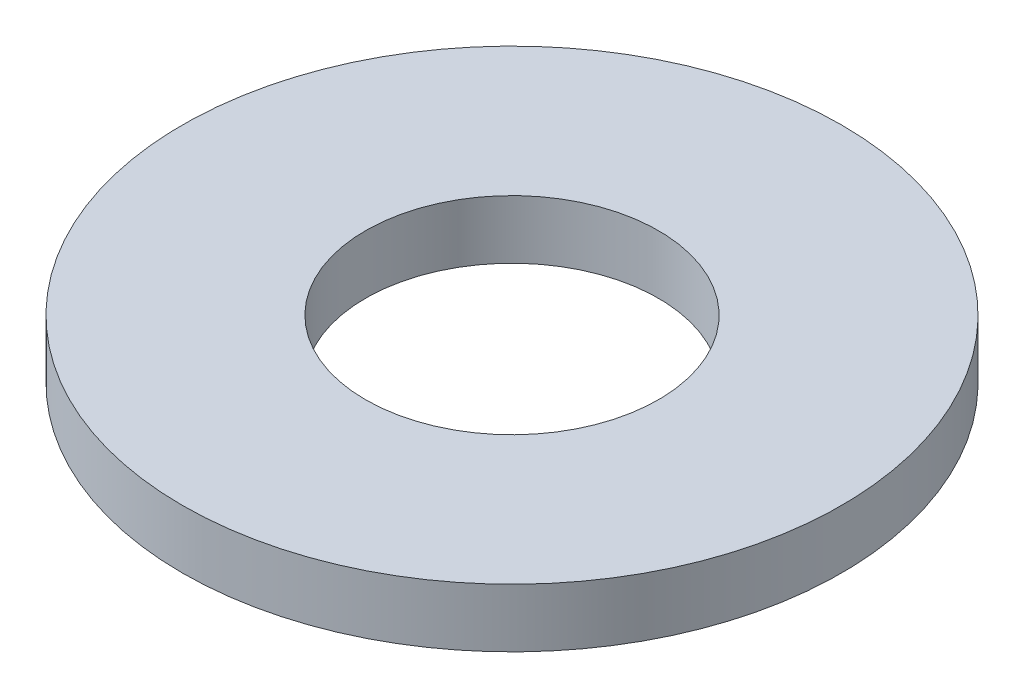
SolidWorks part; units mm, degrees
ref_plane "Front Plane" through (0, 0, 0) normal (0, 0, 1) x (1, 0, 0)
ref_plane "Top Plane" through (0, 0, 0) normal (0, 1, 0) x (1, 0, 0)
ref_plane "Right Plane" through (0, 0, 0) normal (1, 0, 0) x (0, 0, -1)
sketch "Sketch1" plane through (0, 0, 0) normal (0, 1, 0) x (1, 0, 0)
  circle A0 centre (0, 0) radius 22.5
  dimension "FLANGE_OD" = 45
extrude "Boss-Extrude1" add sketch "Sketch1" along normal blind 4
sketch "Sketch2" plane through (0, 0, 0) normal (0, 1, 0) x (1, 0, 0)
  circle A0 centre (0, 0) radius 10
  dimension "BORE_D" = 20
extrude "Cut-Extrude1" cut sketch "Sketch2" along normal through all
sketch "Sketch3" plane through (0, 4, 0) normal (0, 1, 0) x (1, 0, 0)
  circle A0 centre (0, 0) radius 7.1078 construction
  circle A1 centre (-7.1078, 0) radius 2.1256
  dimension "BOLT_D" = 4.2512
  dimension "BOLT_PCD" = 14.2155
extrude "Cut-Extrude2" cut sketch "Sketch3" against normal blind 2.8019 rebuild error yes
pattern_circular "CirPattern1" count 5 over 360 rebuild error yes
